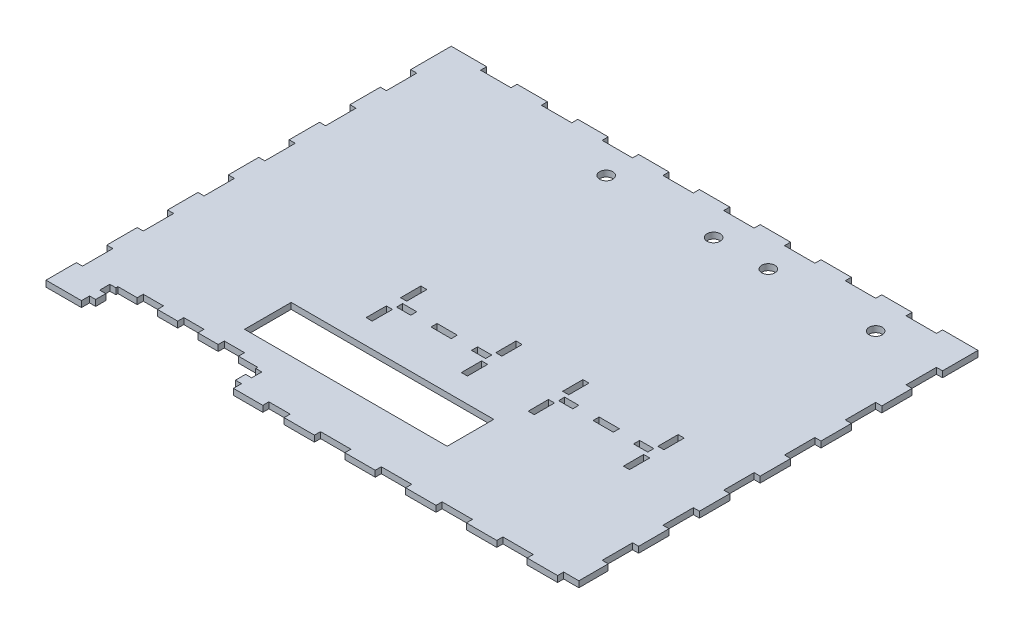
SolidWorks part; units mm, degrees
ref_plane "Alzado" through (0, 0, 0) normal (0, 0, 1) x (1, 0, 0)
ref_plane "Planta" through (0, 0, 0) normal (0, 1, 0) x (1, 0, 0)
ref_plane "Vista lateral" through (0, 0, 0) normal (1, 0, 0) x (0, 0, -1)
sketch "Croquis1" plane through (0, 0, 0) normal (0, 1, 0) x (1, 0, 0)
  line L0 (17.5, 79) -> (20.5, 79)
  line L1 (60, 83) -> (50, 83)
  line L2 (0, 265) -> (17.5, 265)
  line L3 (260, 265) -> (260, 247.5)
  line L4 (252.5, 65) -> (237.5, 65)
  line L5 (50, 83) -> (50, 80)
  line L6 (50, 80) -> (40, 80)
  line L7 (40, 80) -> (40, 83)
  line L8 (84.3736, 80) -> (89.5, 80)
  line L9 (40, 83) -> (30, 83)
  line L10 (17.5, 69) -> (20.5, 69)
  line L11 (0, 65) -> (17.5, 65)
  line L12 (92.5, 69) -> (92.5, 65)
  line L13 (20.5, 74) -> (17.5, 74)
  line L14 (92.5, 69) -> (89.5, 69)
  line L15 (30, 83) -> (30, 80)
  line L16 (89.5, 69) -> (89.5, 74)
  line L17 (92.5, 74) -> (92.5, 79)
  line L18 (115, 143) -> (125, 143)
  line L19 (80, 80) -> (84.3736, 80)
  line L20 (89.5, 80) -> (89.5, 79)
  line L21 (30, 80) -> (25.6264, 80)
  line L22 (115, 140) -> (125, 140)
  line L23 (17.5, 69) -> (17.5, 65)
  line L24 (80, 83) -> (80, 80)
  line L25 (89.5, 74) -> (92.5, 74)
  line L26 (70, 83) -> (80, 83)
  line L27 (120, 93) -> (70, 93)
  line L28 (177.5, 65) -> (177.5, 68)
  line L29 (177.5, 68) -> (162.5, 68)
  line L30 (162.5, 68) -> (162.5, 65)
  line L31 (162.5, 65) -> (147.5, 65)
  line L32 (147.5, 65) -> (147.5, 68)
  line L33 (147.5, 68) -> (132.5, 68)
  line L34 (132.5, 68) -> (132.5, 65)
  line L35 (132.5, 65) -> (117.5, 65)
  line L36 (117.5, 65) -> (117.5, 68)
  line L37 (117.5, 68) -> (107, 68)
  line L38 (107, 68) -> (107, 65)
  line L39 (70, 80) -> (70, 83)
  line L40 (92.5, 65) -> (107, 65)
  line L41 (260, 157.5) -> (257, 157.5)
  line L42 (252.5, 68) -> (260, 68)
  line L43 (252.5, 65) -> (252.5, 68)
  line L44 (237.5, 68) -> (237.5, 65)
  line L45 (222.5, 68) -> (237.5, 68)
  line L46 (222.5, 65) -> (222.5, 68)
  line L47 (207.5, 68) -> (207.5, 65)
  line L48 (192.5, 68) -> (207.5, 68)
  line L49 (192.5, 65) -> (192.5, 68)
  line L50 (257, 157.5) -> (257, 142.5)
  line L51 (257, 142.5) -> (260, 142.5)
  line L52 (260, 142.5) -> (260, 127.5)
  line L53 (260, 127.5) -> (257, 127.5)
  line L54 (257, 127.5) -> (257, 112.5)
  line L55 (257, 112.5) -> (260, 112.5)
  line L56 (260, 112.5) -> (260, 97.5)
  line L57 (260, 97.5) -> (257, 97.5)
  line L58 (257, 97.5) -> (257, 82.5)
  line L59 (257, 82.5) -> (260, 82.5)
  line L60 (89.5, 79) -> (92.5, 79)
  line L61 (257, 247.5) -> (260, 247.5)
  line L62 (257, 232.5) -> (257, 247.5)
  line L63 (260, 232.5) -> (257, 232.5)
  line L64 (257, 217.5) -> (260, 217.5)
  line L65 (257, 202.5) -> (257, 217.5)
  line L66 (260, 202.5) -> (257, 202.5)
  line L67 (257, 187.5) -> (260, 187.5)
  line L68 (257, 172.5) -> (257, 187.5)
  line L69 (260, 172.5) -> (257, 172.5)
  line L70 (137.5, 265) -> (137.5, 262)
  line L71 (137.5, 262) -> (152.5, 262)
  line L72 (152.5, 262) -> (152.5, 265)
  line L73 (152.5, 265) -> (167.5, 265)
  line L74 (167.5, 265) -> (167.5, 262)
  line L75 (167.5, 262) -> (182.5, 262)
  line L76 (182.5, 262) -> (182.5, 265)
  line L77 (182.5, 265) -> (197.5, 265)
  line L78 (197.5, 265) -> (197.5, 262)
  line L79 (197.5, 262) -> (212.5, 262)
  line L80 (212.5, 262) -> (212.5, 265)
  line L81 (212.5, 265) -> (227.5, 265)
  line L82 (227.5, 265) -> (227.5, 262)
  line L83 (227.5, 262) -> (242.5, 262)
  line L84 (242.5, 262) -> (242.5, 265)
  line L85 (17.5, 74) -> (17.5, 79)
  line L86 (17.5, 262) -> (17.5, 265)
  line L87 (32.5, 262) -> (17.5, 262)
  line L88 (32.5, 265) -> (32.5, 262)
  line L89 (47.5, 262) -> (47.5, 265)
  line L90 (62.5, 262) -> (47.5, 262)
  line L91 (62.5, 265) -> (62.5, 262)
  line L92 (77.5, 262) -> (77.5, 265)
  line L93 (92.5, 262) -> (77.5, 262)
  line L94 (92.5, 265) -> (92.5, 262)
  line L95 (107.5, 262) -> (107.5, 265)
  line L96 (122.5, 262) -> (107.5, 262)
  line L97 (122.5, 265) -> (122.5, 262)
  line L98 (0, 140) -> (3, 140)
  line L99 (3, 140) -> (3, 155)
  line L100 (3, 155) -> (0, 155)
  line L101 (0, 155) -> (0, 170)
  line L102 (0, 170) -> (3, 170)
  line L103 (3, 170) -> (3, 185)
  line L104 (3, 185) -> (0, 185)
  line L105 (0, 185) -> (0, 200)
  line L106 (0, 200) -> (3, 200)
  line L107 (3, 200) -> (3, 215)
  line L108 (3, 215) -> (0, 215)
  line L109 (0, 215) -> (0, 230)
  line L110 (0, 230) -> (3, 230)
  line L111 (3, 230) -> (3, 245)
  line L112 (3, 245) -> (0, 245)
  line L113 (20.5, 69) -> (20.5, 74)
  line L114 (60, 80) -> (70, 80)
  line L115 (60, 83) -> (60, 80)
  line L116 (20.5, 79) -> (20.5, 80)
  line L117 (20.5, 80) -> (25.6264, 80)
  line L118 (70, 93) -> (70, 116)
  line L119 (32.5, 265) -> (47.5, 265)
  line L120 (3, 80) -> (0, 80)
  line L121 (3, 95) -> (3, 80)
  line L122 (0, 95) -> (3, 95)
  line L123 (3, 110) -> (0, 110)
  line L124 (3, 125) -> (3, 110)
  line L125 (0, 125) -> (3, 125)
  line L126 (70, 116) -> (170, 116)
  line L127 (170, 116) -> (170, 93)
  line L128 (62.5, 265) -> (77.5, 265)
  line L129 (92.5, 265) -> (107.5, 265)
  line L130 (122.5, 265) -> (137.5, 265)
  line L131 (170, 93) -> (120, 93)
  line L132 (195, 143) -> (205, 143)
  line L134 (242.5, 265) -> (260, 265)
  line L135 (0, 245) -> (0, 265)
  line L139 (0, 125) -> (0, 140)
  line L140 (0, 95) -> (0, 110)
  line L141 (0, 65) -> (0, 80)
  line L142 (142, 138) -> (142, 128)
  line L143 (105, 140) -> (98, 140)
  line L144 (98, 140) -> (98, 143)
  line L145 (98, 143) -> (105, 143)
  line L146 (105, 143) -> (105, 140)
  line L147 (142, 128) -> (145, 128)
  line L148 (98, 145) -> (98, 155)
  line L149 (98, 155) -> (95, 155)
  line L150 (192.5, 65) -> (177.5, 65)
  line L151 (222.5, 65) -> (207.5, 65)
  line L152 (260, 82.5) -> (260, 68)
  line L153 (95, 155) -> (95, 145)
  line L154 (95, 145) -> (98, 145)
  line L155 (260, 172.5) -> (260, 157.5)
  line L156 (260, 202.5) -> (260, 187.5)
  line L157 (260, 232.5) -> (260, 217.5)
  line L158 (145, 128) -> (145, 138)
  line L159 (95, 138) -> (98, 138)
  line L160 (95, 128) -> (95, 138)
  line L161 (98, 128) -> (95, 128)
  line L162 (98, 138) -> (98, 128)
  line L163 (145, 138) -> (142, 138)
  line L164 (145, 145) -> (142, 145)
  line L165 (145, 155) -> (145, 145)
  line L166 (142, 155) -> (145, 155)
  line L167 (142, 145) -> (142, 155)
  line L168 (135, 143) -> (135, 140)
  line L169 (142, 143) -> (135, 143)
  line L170 (142, 140) -> (142, 143)
  line L171 (135, 140) -> (142, 140)
  line L172 (125, 143) -> (125, 140)
  line L173 (115, 140) -> (115, 143)
  line L174 (185, 140) -> (178, 140)
  line L175 (225, 128) -> (225, 138)
  line L176 (178, 140) -> (178, 143)
  line L177 (178, 155) -> (175, 155)
  line L179 (175, 145) -> (178, 145)
  line L180 (222, 140) -> (222, 143)
  line L181 (222, 138) -> (222, 128)
  line L182 (225, 155) -> (225, 145)
  line L184 (222, 128) -> (225, 128)
  line L185 (178, 143) -> (185, 143)
  line L186 (175, 128) -> (175, 138)
  line L187 (205, 140) -> (205, 143)
  line L188 (185, 143) -> (185, 140)
  line L189 (222, 145) -> (222, 155)
  line L190 (222, 155) -> (225, 155)
  line L191 (178, 145) -> (178, 155)
  line L192 (225, 145) -> (222, 145)
  line L194 (178, 128) -> (175, 128)
  line L195 (215, 143) -> (215, 140)
  line L196 (175, 138) -> (178, 138)
  line L197 (225, 138) -> (222, 138)
  line L199 (215, 140) -> (222, 140)
  line L200 (195, 140) -> (205, 140)
  line L201 (175, 155) -> (175, 145)
  line L202 (178, 138) -> (178, 128)
  line L204 (222, 143) -> (215, 143)
  line L205 (195, 140) -> (195, 143)
  circle A0 centre (173.5, 248) radius 3.25
  circle A1 centre (93.5, 248) radius 3.25
  circle A2 centre (146.5, 248) radius 3.25
  circle A3 centre (226.5, 248) radius 3.25
  dimension "D14" = 6.5
  dimension "D16" = 6.5
  dimension "D7" = 50
  dimension "D8" = 10
  dimension "D9" = 10
  dimension "D10" = 23
  dimension "D11" = 100
  dimension "D13" = 10
  dimension "D17" = 3
  dimension "D18" = 3
  dimension "D19" = 15
  dimension "D20" = 15
  dimension "D21" = 15
  dimension "D22" = 15
  dimension "D23" = 15
  dimension "D25" = 3
  dimension "D26" = 15
  dimension "D27" = 15
  dimension "D28" = 15
  dimension "D29" = 15
  dimension "D30" = 15
  dimension "D31" = 15
  dimension "D32" = 15
  dimension "D34" = 3
  dimension "D35" = 15
  dimension "D36" = 15
  dimension "D37" = 15
  dimension "D38" = 15
  dimension "D39" = 15
  dimension "D40" = 15
  dimension "D41" = 15
extrude "Saliente-Extruir1" add sketch "Croquis1" along normal blind 3
